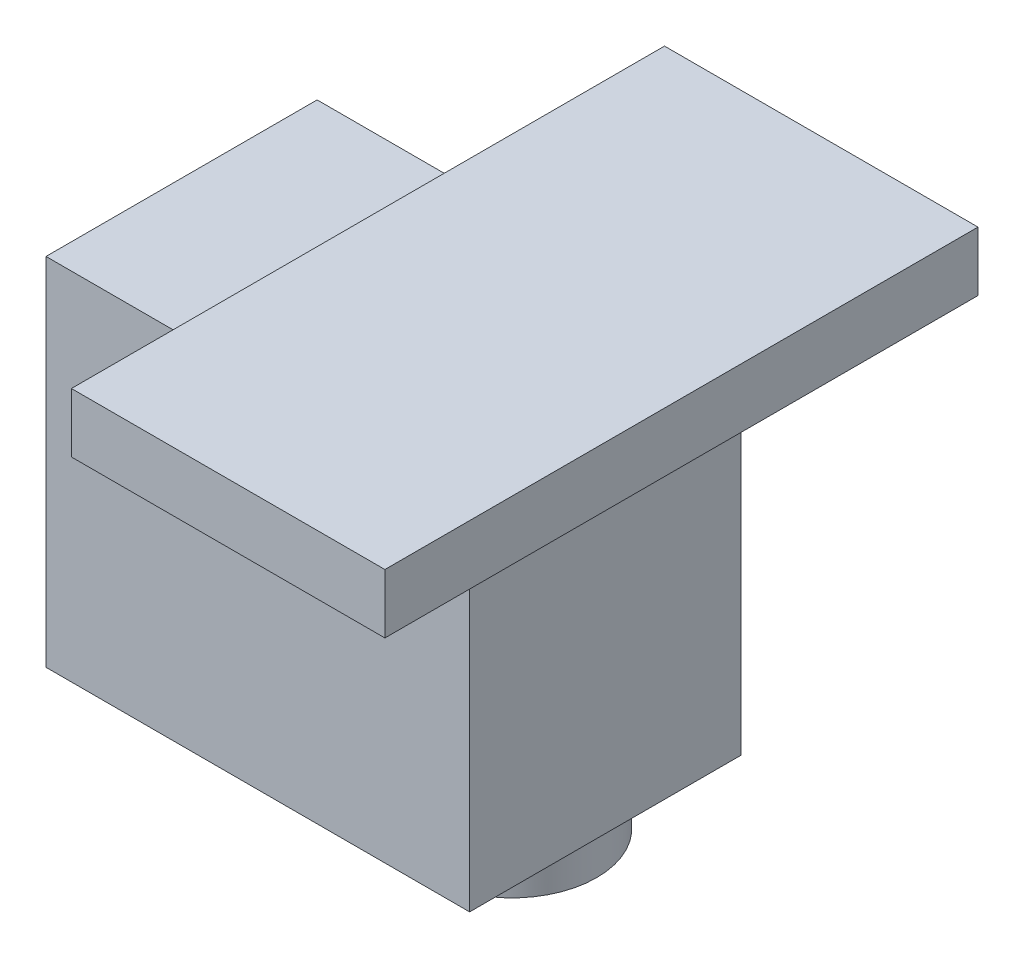
SolidWorks part; units mm, degrees
ref_plane "Front Plane" through (0, 0, 0) normal (0, 0, 1) x (1, 0, 0)
ref_plane "Top Plane" through (0, 0, 0) normal (0, 1, 0) x (1, 0, 0)
ref_plane "Right Plane" through (0, 0, 0) normal (1, 0, 0) x (0, 0, -1)
sketch "Sketch1" plane through (0, 0, 0) normal (0, 0, 1) x (1, 0, 0)
  line L1 (-25, 21) -> (25, 21)
  line L2 (-25, 21) -> (-25, -21)
  line L3 (-25, -21) -> (25, -21)
  line L4 (25, 21) -> (25, -21)
  line L5 (-25, 21) -> (25, -21) construction
  line L6 (-25, -21) -> (25, 21) construction
  line L7 (-3, 21) -> (34, 21)
  line L8 (-3, 21) -> (-3, 28)
  line L9 (-3, 28) -> (34, 28)
  line L10 (34, 21) -> (34, 28)
  point P0 (0, 0)
  point P6 (-3, 21)
  dimension "D1" = 50
  dimension "D2" = 42
  dimension "D3" = 22
  dimension "D4" = 37
  dimension "D5" = 7
extrude "Boss-Extrude1" add sketch "Sketch1" along normal blind 16 contours L4 L1 L2 L3 region at (0, 0, 0)
extrude "Boss-Extrude2" add sketch "Sketch1<3>" against normal blind 16 contours L4 L1 L2 L3 region at (0, 0, 0)
sketch "Sketch1<3>" plane through (0, 0, 0) normal (0, 0, 1) x (1, 0, 0) same geometry as "Sketch1"
extrude "Boss-Extrude3" add sketch "Sketch1<4>" along normal blind 35 contours L7 L10 L9 L8 L1 region at (15.5, 24.5, 0)
sketch "Sketch1<4>" plane through (0, 0, 0) normal (0, 0, 1) x (1, 0, 0) same geometry as "Sketch1"
extrude "Boss-Extrude4" add sketch "Sketch1<5>" against normal blind 35 contours L7 L10 L9 L8 L1 region at (15.5, 24.5, 0)
sketch "Sketch1<5>" plane through (0, 0, 0) normal (0, 0, 1) x (1, 0, 0) same geometry as "Sketch1"
sketch "Sketch3" plane through (0, -21, 0) normal (0, -1, 0) x (1, 0, 0)
  line L0 (25, 16) -> (25, -16) construction
  line L1 (25, 0) -> (14, 0)
  line L2 (25, 16) -> (25, -16) construction
  circle A0 centre (14, 0) radius 10
  point P0 (25, 0)
  dimension "D1" = 11
extrude "Boss-Extrude5" add sketch "Sketch3" along normal blind 5 contours A0 region at (4.2828, -21, 0)
ref_point "Point1"
